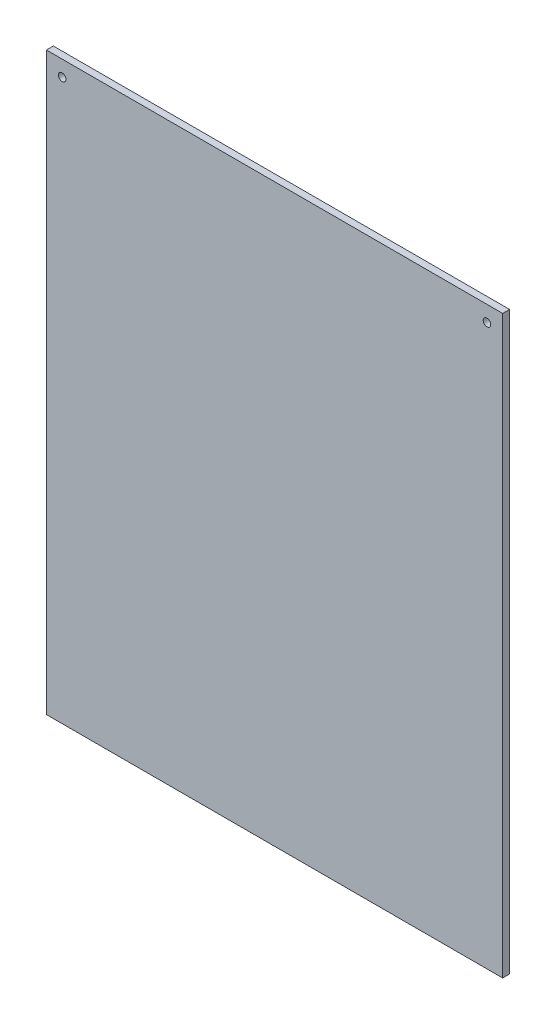
SolidWorks part; units mm, degrees
ref_plane "Front Plane" through (0, 0, 0) normal (0, 0, 1) x (1, 0, 0)
ref_plane "Top Plane" through (0, 0, 0) normal (0, 1, 0) x (1, 0, 0)
ref_plane "Right Plane" through (0, 0, 0) normal (1, 0, 0) x (0, 0, -1)
sketch "Sketch1" plane through (0, 0, 0) normal (0, 0, 1) x (1, 0, 0)
  line L0 (81.8848, 154.8822) -> (81.8848, -120.1178)
  line L1 (81.8848, 154.8822) -> (-136.1152, 154.8822)
  line L2 (81.8848, -120.1178) -> (-136.1152, -120.1178)
  line L3 (-136.1152, 154.8822) -> (-136.1152, -120.1178)
  circle A0 centre (-128.6152, 147.3822) radius 1.8
  circle A1 centre (74.3848, 147.3822) radius 1.8
  dimension "D3" = 7.5
  dimension "D1" = 275
  dimension "D2" = 218
  dimension "D4" = 7.5
  dimension "D5" = 7.5
  dimension "D6" = 7.5
extrude "Boss-Extrude1" add sketch "Sketch1" along normal blind 3.302
